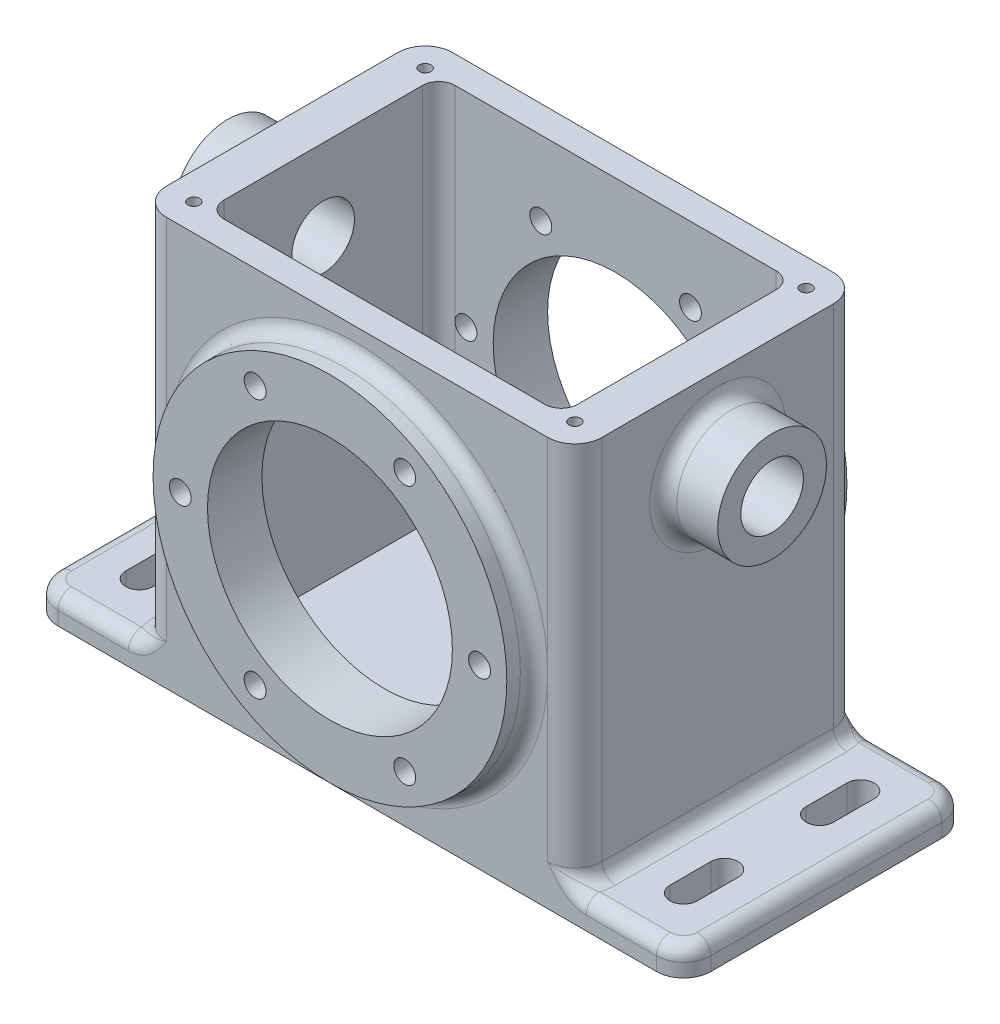
SolidWorks part; units mm, degrees
material "Cast Alloy Steel"
ref_plane "Front Plane" through (0, 0, 0) normal (0, 0, 1) x (1, 0, 0)
ref_plane "Top Plane" through (0, 0, 0) normal (0, 1, 0) x (1, 0, 0)
ref_plane "Right Plane" through (0, 0, 0) normal (1, 0, 0) x (0, 0, -1)
sketch "Base Sketch" plane through (0, 0, 0) normal (0, 1, 0) x (1, 0, 0)
  line L0 (-76.2, 33.3375) -> (76.2, -33.3375) construction
  line L1 (-76.2, 33.3375) -> (76.2, 33.3375)
  line L2 (-76.2, 33.3375) -> (-76.2, -33.3375)
  line L3 (-76.2, -33.3375) -> (76.2, -33.3375)
  line L4 (76.2, 33.3375) -> (76.2, -33.3375)
  dimension "D1" = 152.4
  dimension "D2" = 66.675
extrude "Base Body" add sketch "Base Sketch" along normal blind 6.35
sketch "Secondary Sketch" plane through (0, 6.35, 0) normal (0, 1, 0) x (1, 0, 0)
  line L0 (76.2, 33.3375) -> (-76.2, 33.3375) construction
  line L1 (50.8, -33.3375) -> (-50.8, -33.3375)
  line L2 (50.8, -33.3375) -> (50.8, 33.3375)
  line L3 (50.8, 33.3375) -> (-50.8, 33.3375)
  line L4 (-50.8, -33.3375) -> (-50.8, 33.3375)
  line L5 (50.8, -33.3375) -> (-50.8, 33.3375) construction
  line L6 (50.8, 33.3375) -> (-50.8, -33.3375) construction
  point P0 (0, 0)
  dimension "D1" = 101.6
extrude "Secondary Body" add sketch "Secondary Sketch" along normal blind 88.9
fillet "Corner Fillet" radius 6.35 8 edges at (76.2, 3.175, 33.3375) (76.2, 3.175, -33.3375) (-76.2, 3.175, 33.3375) (-76.2, 3.175, -33.3375) (-50.8, 50.8, -33.3375) (-50.8, 50.8, 33.3375) (50.8, 50.8, -33.3375) (50.8, 50.8, 33.3375)
fillet "Face Fillet" radius 3.175 16 edges at (48.9401, 6.35, 31.4776) (50.8, 6.35, 0) (48.9401, 6.35, -31.4776) (57.15, 6.35, -33.3375) (74.3401, 6.35, -31.4776) (76.2, 6.35, 0) (74.3401, 6.35, 31.4776) (57.15, 6.35, 33.3375) (-74.3401, 6.35, -31.4776) (-57.15, 6.35, -33.3375) (-48.9401, 6.35, -31.4776) (-50.8, 6.35, 0) (-48.9401, 6.35, 31.4776) (-57.15, 6.35, 33.3375) (-74.3401, 6.35, 31.4776) (-76.2, 6.35, 0)
sketch "Top Sketch" plane through (0, 95.25, 0) normal (0, 1, 0) x (1, 0, 0)
  line L0 (44.45, 33.3375) -> (-44.45, 33.3375) construction
  line L1 (-37.465, 26.9875) -> (37.465, 26.9875)
  line L2 (-41.275, 23.1775) -> (-41.275, -23.1775)
  line L3 (-37.465, -26.9875) -> (37.465, -26.9875)
  line L4 (41.275, 23.1775) -> (41.275, -23.1775)
  line L5 (50.8, -26.9875) -> (50.8, 26.9875) construction
  line L6 (-44.45, -33.3375) -> (44.45, -33.3375) construction
  line L7 (-50.8, 26.9875) -> (-50.8, -26.9875) construction
  arc A0 (-41.275, -23.1775) -> (-37.465, -26.9875) centre (-37.465, -23.1775) ccw
  arc A1 (37.465, -26.9875) -> (41.275, -23.1775) centre (37.465, -23.1775) ccw
  arc A2 (37.465, 26.9875) -> (41.275, 23.1775) centre (37.465, 23.1775) cw
  arc A3 (-37.465, 26.9875) -> (-41.275, 23.1775) centre (-37.465, 23.1775) ccw
  dimension "D5" = 3.81
  dimension "D1" = 6.35
  dimension "D2" = 9.525
  dimension "D3" = 6.35
  dimension "D4" = 9.525
extrude "Top Cut" cut sketch "Top Sketch" against normal blind 88.9
sketch "Front Sketch" plane through (0, 0, 33.3375) normal (0, 0, 1) x (1, 0, 0)
  line L0 (-44.45, 95.25) -> (44.45, 95.25) construction
  circle A0 centre (0, 47.625) radius 41.275
  dimension "D1" = 47.625
  dimension "D2" = 82.55
extrude "Front Boss" add sketch "Front Sketch" along normal blind 6.35
mirror "Face Mirror" about plane through (0, 0, 0) normal (0, 0, 1) of "Front Boss"
sketch "Boss Sketch" plane through (50.8, 0, 0) normal (1, 0, 0) x (0, 0, -1)
  line L0 (-26.9875, 95.25) -> (26.9875, 95.25) construction
  circle A0 centre (0, 76.2) radius 12.7
  dimension "D1" = 25.4
  dimension "D2" = 19.05
extrude "Side Boss" add sketch "Boss Sketch" along normal blind 12.7
mirror "Side Mirror" about plane through (0, 0, 0) normal (1, 0, 0) of "Side Boss"
sketch "Center Sketch" plane through (0, 0, 39.6875) normal (0, 0, 1) x (1, 0, 0)
  circle A0 centre (0, 47.625) radius 28.575
  circle A1 centre (0, 47.625) radius 41.275 construction
  dimension "D1" = 57.15
extrude "Center Extrude" cut sketch "Center Sketch" against normal through all
sketch "Side Sketch" plane through (63.5, 0, 0) normal (1, 0, 0) x (0, 0, -1)
  circle A0 centre (0, 76.2) radius 7.3025
  circle A1 centre (0, 76.2) radius 12.7 construction
  dimension "D1" = 14.605
extrude "Side Extrude" cut sketch "Side Sketch" against normal through all contours A0
hole_wizard "1/4-20 Circular Screws" positions "Screw Width" profile "Screw Depth" tap size "1/4-20" standard "ANSI Inch" end condition through all
sketch "Screw Width" plane through (0, 0, 39.6875) normal (0, 0, 1) x (1, 0, 0)
  line L0 (-41.275, 47.625) -> (-28.575, 47.625) construction
  circle A0 centre (0, 47.625) radius 41.275 construction
  circle A1 centre (0, 47.625) radius 41.275 construction
  circle A2 centre (0, 47.625) radius 28.575 construction
  point P12 (-34.925, 47.625)
cosmetic thread "Hole Thread1" parameters "D2"=6.35
sketch "Screw Depth" plane through (-34.925, 47.625, 39.6875) normal (1, 0, 0) x (0, -1, 0)
  line L0 (0, 0) -> (0, 79.375)
  line L1 (0, 79.375) -> (2.5527, 79.375)
  line L2 (2.5527, 79.375) -> (2.5527, 0)
  line L5 (2.5527, 0) -> (0, 0)
  line L11 (0, -6.35) -> (0, 107.95) construction
  dimension "Thru Tap Drill Dia." = 5.1054
  dimension "Thru Tap Drill Depth" = 79.375
pattern_circular "Screw Pattern" count 6 over 360 about axis through (0, 47.625, -39.6875) along (0, 0, 1) of "1/4-20 Circular Screws" reverse direction yes
mirror "Middle Mirror" about plane through (0, 0, 0) normal (0, 0, 1) of "Screw Pattern"
hole_wizard "#6-32 Corner Holes" positions "Hole Width" profile "Hole Depth" tap size "#6-32" standard "ANSI Inch"
sketch "Hole Width" plane through (0, 95.25, 0) normal (0, 1, 0) x (1, 0, 0)
  point P0 (-44.45, 26.9875)
  point P3 (44.45, 26.9875)
  point P6 (44.45, -26.9875)
  point P9 (-44.45, -26.9875)
sketch "Hole Depth" plane through (-44.45, 95.25, -26.9875) normal (1, 0, 0) x (0, 0, 1)
  line L0 (0, 0) -> (0, 11.7855)
  line L1 (0, 11.7855) -> (1.3525, 10.9728)
  line L2 (1.3525, 10.9728) -> (1.3525, 0)
  line L5 (1.3525, 0) -> (0, 0)
  line L10 (0, 11.7855) -> (-1.3525, 10.9728) construction
  line L11 (0, -6.35) -> (0, 107.95) construction
  dimension "Tap Drill Dia." = 2.7051
  dimension "Tap Drill Depth" = 10.9728
  dimension "Drill Angle" = 118
cosmetic thread "Hole Thread6" parameters "D1"=9.7028, "D2"=3.5052
cosmetic thread "Hole Thread7" parameters "D1"=9.7028, "D2"=3.5052
cosmetic thread "Hole Thread8" parameters "D1"=9.7028, "D2"=3.5052
cosmetic thread "Hole Thread9" parameters "D1"=9.7028, "D2"=3.5052
sketch "Slot Sketch" plane through (0, 6.35, 0) normal (0, 1, 0) x (1, 0, 0)
  line L0 (-63.5, -20.6375) -> (-63.5, -11.1125) construction
  line L1 (-66.675, -20.6375) -> (-66.675, -11.1125)
  line L2 (-60.325, -20.6375) -> (-60.325, -11.1125)
  line L3 (-53.4303, -33.3375) -> (-69.85, -33.3375) construction
  line L4 (-76.2, -26.9875) -> (-76.2, 26.9875) construction
  arc A0 (-66.675, -20.6375) -> (-60.325, -20.6375) centre (-63.5, -20.6375) ccw
  arc A1 (-60.325, -11.1125) -> (-66.675, -11.1125) centre (-63.5, -11.1125) ccw
  point P2 (-63.5, -15.875)
  dimension "D3" = 12.7
  dimension "D1" = 6.35
  dimension "D2" = 9.525
  dimension "D4" = 12.7
extrude "Slot" cut sketch "Slot Sketch" against normal through all
pattern_linear "Slot Pattern" count 2 spacing 31.75 along (0, 0, -1) of "Slot"
mirror "Slot Mirror" about plane through (0, 0, 0) normal (1, 0, 0) of "Slot Pattern"
fillet "Round Fillet" radius 3.175 4 edges at (41.275, 47.625, -33.3375) (-50.8, 76.2, -12.7) (50.8, 76.2, 12.7) (-41.275, 47.625, 33.3375)
